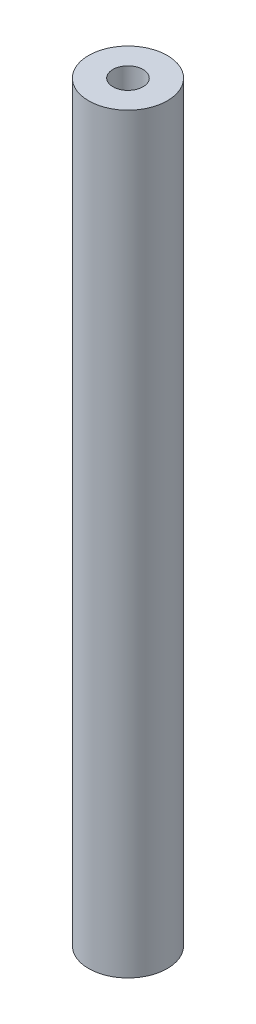
SolidWorks part; units mm, degrees
ref_plane "Front Plane" through (0, 0, 0) normal (0, 0, 1) x (1, 0, 0)
ref_plane "Top Plane" through (0, 0, 0) normal (0, 1, 0) x (1, 0, 0)
ref_plane "Right Plane" through (0, 0, 0) normal (1, 0, 0) x (0, 0, -1)
sketch "Sketch1" plane through (0, 0, 0) normal (0, 1, 0) x (1, 0, 0)
  circle A0 centre (0, 0) radius 1.15
  circle A1 centre (0, 0) radius 3
  dimension "D1" = 2.3
  dimension "D2" = 6
extrude "Boss-Extrude1" add sketch "Sketch1" along normal blind 57.33
